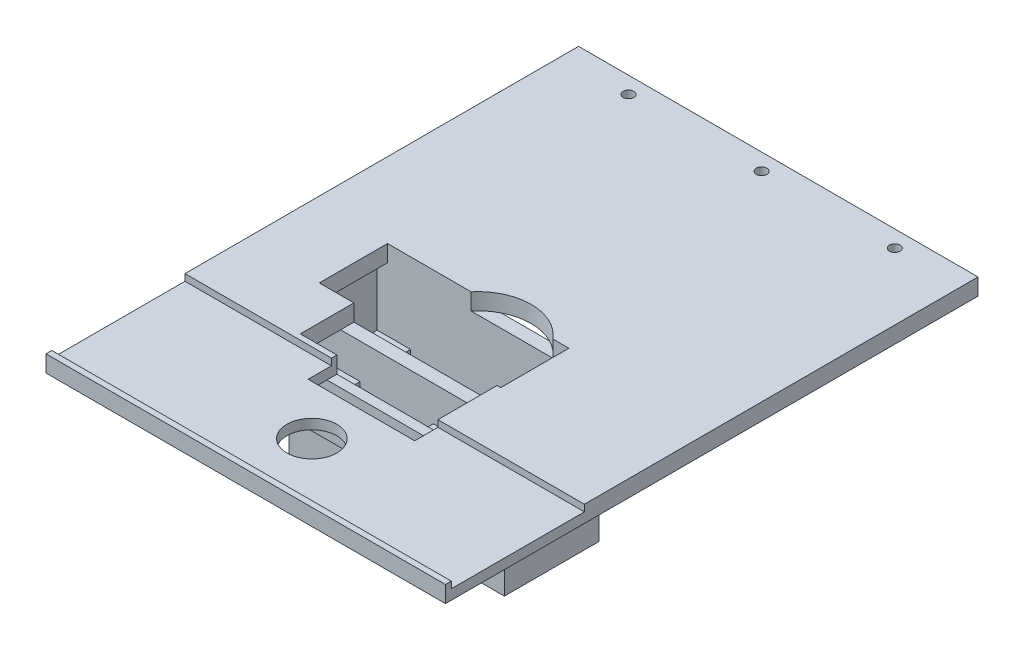
SolidWorks part; units mm, degrees
ref_plane "Front Plane" through (0, 0, 0) normal (0, 0, 1) x (1, 0, 0)
ref_plane "Top Plane" through (0, 0, 0) normal (0, 1, 0) x (1, 0, 0)
ref_plane "Right Plane" through (0, 0, 0) normal (1, 0, 0) x (0, 0, -1)
sketch "Sketch1" plane through (0, 0, 0) normal (0, 1, 0) x (1, 0, 0)
  line L1 (0, 0) -> (120, 0)
  line L2 (0, 0) -> (0, 160)
  line L3 (0, 160) -> (120, 160)
  line L4 (120, 0) -> (120, 160)
  dimension "D1" = 120
  dimension "D2" = 160
extrude "Boss-Extrude1" add sketch "Sketch1" along normal blind 5
sketch "Sketch2" plane through (0, 5, 0) normal (0, 1, 0) x (1, 0, 0)
  line L1 (0, 160) -> (0, 0) construction
  line L2 (120, 160) -> (0, 160) construction
  circle A0 centre (60, 69.75) radius 16
  dimension "D1" = 90.25
  dimension "D2" = 60
  dimension "D3" = 32
extrude "Cut-Extrude1" cut sketch "Sketch2" against normal up to next
sketch "Sketch3" plane through (0, 5, 0) normal (0, 1, 0) x (1, 0, 0)
  line L0 (44, 69.75) -> (44, 34.75)
  line L1 (44, 34.75) -> (76, 34.75)
  line L2 (76, 34.75) -> (76, 69.75)
  line L3 (44, 69.75) -> (76, 69.75)
  circle A0 centre (60, 69.75) radius 16 construction
  dimension "D1" = 35
extrude "Cut-Extrude2" cut sketch "Sketch3" against normal up to next
sketch "Sketch4" plane through (0, 5, 0) normal (0, 1, 0) x (1, 0, 0)
  line L0 (0, 160) -> (0, 0) construction
  line L1 (0, 41.75) -> (120, 41.75)
  line L2 (0, 41.75) -> (0, 1.75)
  line L3 (0, 1.75) -> (120, 1.75)
  line L4 (120, 41.75) -> (120, 1.75)
  line L5 (120, 0) -> (120, 160) construction
  line L6 (44, 34.75) -> (76, 34.75) construction
  dimension "D1" = 7
  dimension "D2" = 40
extrude "Cut-Extrude3" cut sketch "Sketch4" against normal blind 2
sketch "Sketch5" plane through (0, 5, 0) normal (0, 1, 0) x (1, 0, 0)
  line L0 (120, 160) -> (0, 160) construction
  line L1 (0, 160) -> (0, 41.75) construction
  line L2 (120, 41.75) -> (120, 160) construction
  point P0 (20, 155)
  point P2 (60, 155)
  point P4 (100, 155)
  dimension "D1" = 5
  dimension "D2" = 20
  dimension "D3" = 60
  dimension "D4" = 20
hole_wizard "Ø3.0mm Dowel Hole1" positions "Sketch5" profile "Sketch6" hole size "Ø3.0" standard "ANSI Metric"
sketch "Sketch6" plane through (20, 5, -155) normal (1, 0, 0) x (0, 0, 1)
  line L0 (0, 0) -> (0, 15.9614)
  line L1 (0, 15.9614) -> (1.6, 15)
  line L2 (1.6, 15) -> (1.6, 0)
  line L5 (1.6, 0) -> (0, 0)
  line L10 (0, 15.9614) -> (-1.6, 15) construction
  line L11 (0, -6.35) -> (0, 107.95) construction
  dimension "Hole Dia." = 3.2
  dimension "Hole Depth" = 15
  dimension "Drill Angle" = 118
sketch "Sketch7" plane through (0, 0, 0) normal (0, -1, 0) x (1, 0, 0)
  line L0 (120, 0) -> (120, -160) construction
  line L1 (0, -43.4) -> (120, -43.4)
  line L2 (0, -43.4) -> (0, -40.4)
  line L3 (0, -40.4) -> (120, -40.4)
  line L4 (120, -43.4) -> (120, -40.4)
  line L6 (120, -160) -> (0, -160) construction
  line L7 (0, -160) -> (0, 0) construction
  line L8 (0, -55.5) -> (120, -55.5)
  line L9 (0, -55.5) -> (0, -59.5)
  line L10 (0, -59.5) -> (120, -59.5)
  line L11 (120, -55.5) -> (120, -59.5)
  line L13 (0, -80) -> (120, -80)
  line L14 (0, -80) -> (0, -84)
  line L15 (0, -84) -> (120, -84)
  line L16 (120, -80) -> (120, -84)
  dimension "D1" = 116.6
  dimension "D2" = 3
  dimension "D3" = 4
  dimension "D4" = 4
  dimension "D5" = 100.5
  dimension "D6" = 80
extrude "Boss-Extrude2" add sketch "Sketch7" along normal blind 44.7
sketch "Sketch8" plane through (0, 0, 0) normal (0, -1, 0) x (1, 0, 0)
  line L1 (22.6, -80) -> (77.1, -80)
  line L2 (22.6, -80) -> (22.6, -59.5)
  line L3 (22.6, -59.5) -> (77.1, -59.5)
  line L4 (77.1, -80) -> (77.1, -59.5)
  line L5 (76, -59.5) -> (120, -59.5) construction
  line L6 (0, -80) -> (0, -59.5) construction
  dimension "D1" = 54.5
  dimension "D2" = 22.6
extrude "Cut-Extrude4" cut sketch "Sketch8" against normal blind 20
sketch "Sketch9" plane through (0, 0, 0) normal (0, -1, 0) x (1, 0, 0)
  line L1 (44, -43.4) -> (33, -43.4)
  line L2 (44, -43.4) -> (44, -59.5)
  line L3 (44, -59.5) -> (33, -59.5)
  line L4 (33, -43.4) -> (33, -59.5)
  line L5 (0, -59.5) -> (120, -59.5) construction
  dimension "D1" = 11
extrude "Cut-Extrude5" cut sketch "Sketch9" against normal blind 20
sketch "Sketch10" plane through (0, 0, -59.5) normal (0, 0, -1) x (-1, 0, 0)
  line L0 (-120, 0) -> (0, 0) construction
  line L1 (-29.5, -19.1) -> (-19.5, -19.1)
  line L2 (-29.5, -19.1) -> (-29.5, -23.1)
  line L3 (-29.5, -23.1) -> (-19.5, -23.1)
  line L4 (-19.5, -19.1) -> (-19.5, -23.1)
  line L5 (0, -44.7) -> (0, 0) construction
  line L7 (-70.2, -19.1) -> (-80.2, -19.1)
  line L8 (-70.2, -19.1) -> (-70.2, -23.1)
  line L9 (-70.2, -23.1) -> (-80.2, -23.1)
  line L10 (-80.2, -19.1) -> (-80.2, -23.1)
  dimension "D1" = 19.1
  dimension "D2" = 29.5
  dimension "D3" = 10
  dimension "D4" = 4
  dimension "D5" = 4
  dimension "D6" = 10
  dimension "D7" = 40.7
extrude "Boss-Extrude3" add sketch "Sketch10" along normal up to next
sketch "Sketch11" plane through (0, 0, -43.4) normal (0, 0, -1) x (-1, 0, 0)
  line L0 (0, 0) -> (-33, 0) construction
  line L1 (-19.5, -10.53) -> (-38.85, -10.53)
  line L2 (-19.5, -10.53) -> (-19.5, -15.53)
  line L3 (-19.5, -15.53) -> (-38.85, -15.53)
  line L4 (-38.85, -10.53) -> (-38.85, -15.53)
  line L5 (0, -44.7) -> (0, 0) construction
  line L7 (-19.5, -23.1) -> (-19.5, -19.1) construction
  line L8 (-80.2, -19.1) -> (-80.2, -23.1) construction
  line L9 (-60.85, -10.53) -> (-80.2, -10.53)
  line L10 (-60.85, -10.53) -> (-60.85, -15.53)
  line L11 (-60.85, -15.53) -> (-80.2, -15.53)
  line L12 (-80.2, -10.53) -> (-80.2, -15.53)
  dimension "D1" = 10.53
  dimension "D2" = 38.85
  dimension "D3" = 22
  dimension "D4" = 5
extrude "Boss-Extrude4" add sketch "Sketch11" along normal up to vertex up to point (80.2, -21.1, -59.5)
sketch "Sketch12" plane through (0, -44.7, 0) normal (0, -1, 0) x (1, 0, 0)
  line L1 (0, -40.4) -> (120, -40.4)
  line L2 (0, -40.4) -> (0, -43.4)
  line L3 (0, -43.4) -> (120, -43.4)
  line L4 (120, -40.4) -> (120, -43.4)
extrude "Cut-Extrude6" cut sketch "Sketch12" against normal up to surface (29.17 mm away)
sketch "Sketch13" plane through (0, 0, -84) normal (0, 0, -1) x (-1, 0, 0)
  line L0 (0, -44.7) -> (-120, -44.7) construction
  line L1 (0, 0) -> (-19.5, 0)
  line L2 (0, 0) -> (0, -44.7)
  line L3 (0, -44.7) -> (-19.5, -44.7)
  line L4 (-19.5, 0) -> (-19.5, -44.7)
  line L5 (-67.2758, 0) -> (-120, 0) construction
  line L6 (-120, -44.7) -> (-80.2, -44.7)
  line L7 (-120, -44.7) -> (-120, 0)
  line L8 (-120, 0) -> (-80.2, 0)
  line L9 (-80.2, -44.7) -> (-80.2, 0)
  line L10 (-19.5, -10.53) -> (-19.5, -15.53) construction
  line L11 (-80.2, -15.53) -> (-80.2, -10.53) construction
extrude "Cut-Extrude7" cut sketch "Sketch13" against normal through all
ref_plane "Plane1" through (49.85, 0, 0) normal (-1, 0, 0) x (0, 0, 1)
sketch "Sketch14" plane through (80.2, 0, 0) normal (1, 0, 0) x (0, 0, -1)
  line L1 (40.4, 0) -> (84, 0)
  line L2 (40.4, 0) -> (40.4, -15.53)
  line L3 (55.5, -44.7) -> (84, -44.7)
  line L4 (84, 0) -> (84, -44.7)
  line L5 (40.4, -15.53) -> (55.5, -15.53)
  line L8 (55.5, -15.53) -> (55.5, -44.7)
extrude "Boss-Extrude5" add sketch "Sketch14" along normal blind 2
mirror "Mirror1" about plane through (49.85, 0, 0) normal (-1, 0, 0) of "Boss-Extrude5"
sketch "Sketch15" plane through (0, 3, 0) normal (0, 1, 0) x (1, 0, 0)
  line L0 (120, 1.75) -> (120, 41.75) construction
  line L1 (0, 0) -> (120, 0) construction
  circle A0 centre (60, 19.87) radius 7.5
  dimension "D1" = 15
  dimension "D2" = 60
  dimension "D3" = 19.87
extrude "Cut-Extrude8" cut sketch "Sketch15" against normal blind 10
sketch "Sketch16" plane through (0, -10.53, 0) normal (0, 1, 0) x (1, 0, 0)
  circle A0 centre (35.85, 49.49) radius 1
  circle A1 centre (63.85, 49.49) radius 1
extrude "Cut-Extrude9" cut sketch "Sketch16" against normal up to next
sketch "Sketch17" plane through (0, -19.1, 0) normal (0, 1, 0) x (1, 0, 0)
  circle A0 centre (25.35, 74.75) radius 1.71
  circle A1 centre (25.35, 64.75) radius 1.71
  circle A2 centre (74.35, 74.75) radius 1.71
  circle A3 centre (74.35, 64.75) radius 1.71
extrude "Cut-Extrude10" cut sketch "Sketch17" against normal up to next
